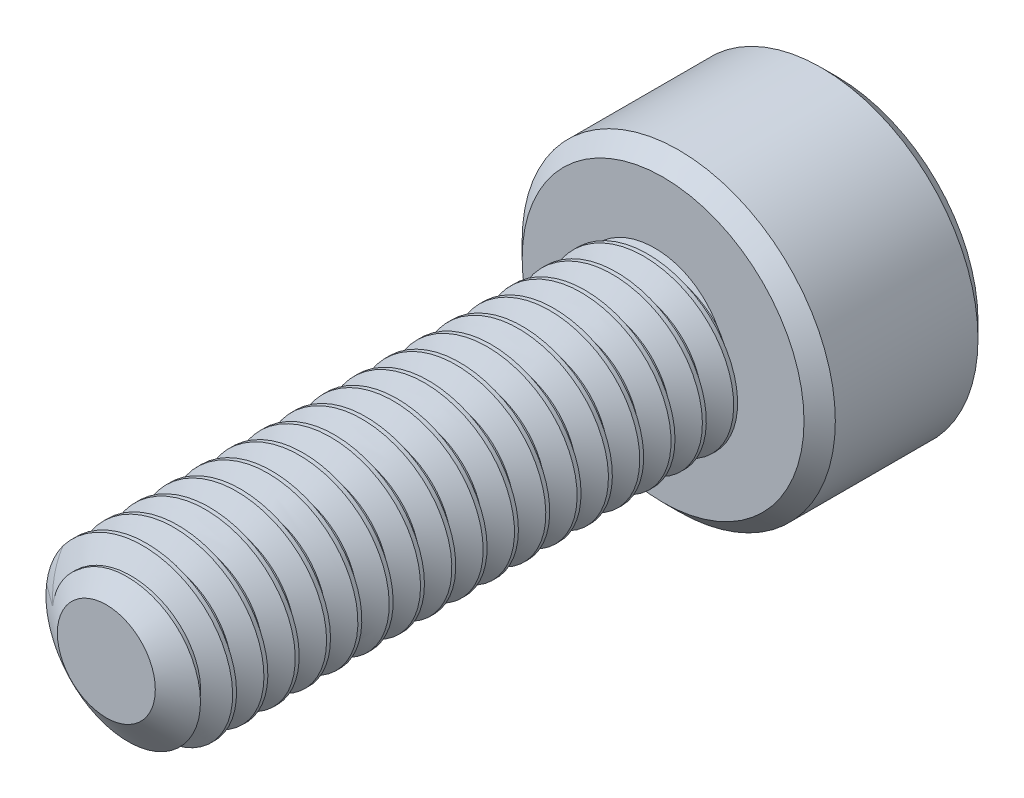
SolidWorks part; units mm, degrees
other "DetailItem1"
ref_plane "Front Plane" through (0, 0, 0) normal (0, 0, 1) x (1, 0, 0)
ref_plane "Top Plane" through (0, 0, 0) normal (0, 1, 0) x (1, 0, 0)
ref_plane "Right Plane" through (0, 0, 0) normal (1, 0, 0) x (0, 0, -1)
sketch "Sketch1" plane through (0, 0, 0) normal (0, 0, 1) x (1, 0, 0)
  circle A0 centre (0, 0) radius 1.25
  dimension "OD" = 2.5
extrude "Extrude1" add sketch "Sketch1" against normal blind 8
sketch "Sketch2" plane through (0, 0, 0) normal (0, 0, 1) x (1, 0, 0)
  circle A0 centre (0, 0) radius 1.25 construction
  circle A1 centre (0, 0) radius 1.25
curve "Helix/Spiral1" pitch 0.45 height 8.45 radius 1.25 centre (0, 0, 0) axis (0, 0, -1) start towards (0, 1, 0) parameters "pitch"=0.45
sketch "Sketch3" plane through (0, 0, 0) normal (1, 0, 0) x (0, 0, -1)
  line L0 (-0.3937, 1.25) -> (-0.225, 0.9577)
  line L1 (-0.225, 0.9577) -> (-0.1688, 0.9577)
  line L2 (-0.1688, 0.9577) -> (0, 1.25)
  line L3 (-0.3937, 1.25) -> (0, 1.25)
  line L4 (-0.1969, 1.25) -> (-0.1969, 0.9577) construction
  line L5 (-0.3094, 1.1039) -> (-0.0844, 1.1039) construction
  line L6 (0, 1.25) -> (0, -1.25) construction
  dimension "D1" = 0.0563
  dimension "D2" = 0.225
  dimension "D3" = 60
sweep "Cut-Sweep1" cut profiles "Sketch3" path "Helix/Spiral1" align with end faces yes
sketch "Sketch4" plane through (0, 0, 0) normal (1, 0, 0) x (0, 0, -1)
  line L0 (0.3825, 1.25) -> (0, 0.7037)
  line L1 (0, 0.7037) -> (0, 1.25)
  line L2 (0.3825, 1.25) -> (0, 1.25)
  line L3 (-0.3937, 1.25) -> (0, 1.25) construction
  line L4 (0, 0) -> (7.0209, 0) construction
  dimension "D1" = 55
  dimension "D2" = 0.254
revolve "Cut-Revolve1" cut sketch "Sketch4" angle 360 about L4
sketch "Sketch6" plane through (0, 0, -8) normal (0, 0, -1) x (-1, 0, 0)
  circle A0 centre (0, 0) radius 2.25
  dimension "head dia" = 4.5
extrude "Extrude2" add sketch "Sketch6" along normal blind 2.5
sketch "Sketch7" plane through (0, 0, -10.5) normal (0, 0, -1) x (-1, 0, 0)
  line L1 (0, 1.1547) -> (-1, 0.5774)
  line L2 (-1, 0.5774) -> (-1, -0.5774)
  line L3 (-1, -0.5774) -> (0, -1.1547)
  line L4 (0, -1.1547) -> (1, -0.5774)
  line L5 (1, -0.5774) -> (1, 0.5774)
  line L6 (1, 0.5774) -> (0, 1.1547)
  circle A0 centre (0, 0) radius 1 construction
  dimension "hex dia" = 2
extrude "Cut-Extrude1" cut sketch "Sketch7" against normal blind 1.5
sketch "Sketch8" plane through (0, 0, -10.5) normal (0, 0, -1) x (-1, 0, 0)
  circle A0 centre (0, 0) radius 1.1547
extrude "Cut-Extrude2" cut sketch "Sketch8" against normal through all draft 45
chamfer "Chamfer1" distance 0.225 angle 45 2 edges at (-2.25, 0, -10.5) (-2.25, 0, -8)
sketch "Sketch10" plane through (0, 0, -8) normal (0, 0, 1) x (1, 0, 0)
  circle A1 centre (0, 0) radius 1.25
  circle A2 centre (0, 0) radius 1.25
  dimension "D1" = 0
ref_plane "Plane1" through (0, 0, 0) normal (0, 0, 1) x (1, 0, 0)
extrude "partial thread" [suppressed] add sketch "Sketch10" along normal up to surface (8 mm away) separate body up to plane "Plane1"
chamfer "Chamfer2" [suppressed] distance 0.05 angle 45
combine bodies "Combine1" [suppressed] operation type add bodies to combine 107 108
sketch "Sketch9" plane through (0, 0, 0) normal (1, 0, 0) x (0, 0, -1)
  line L0 (0, 1.25) -> (0, -1.25) construction
  line L1 (1.125, 1.25) -> (1.125, -1.25) construction
  dimension "D1" = 1.125
equation "\"D3@Helix/Spiral1\" = \"screw length@Extrude1\"+\"pitch@Helix/Spiral1\""
equation "\"D1@Sketch3\" = \"pitch@Helix/Spiral1\"*.125"
equation "\"D2@Sketch3\" = \"pitch@Helix/Spiral1\"*.5"
equation "\"D1@Cut-Extrude1\" = \"hex dia@Sketch7\"*.75"
equation "\"D1@Chamfer1\" = \"head dia@Sketch6\"*.05"
equation "\"D1@Sketch9\" = \"pitch@Helix/Spiral1\"*2.5"
equation "\"D1@Chamfer2\"=\"OD@Sketch1\"*.02"
